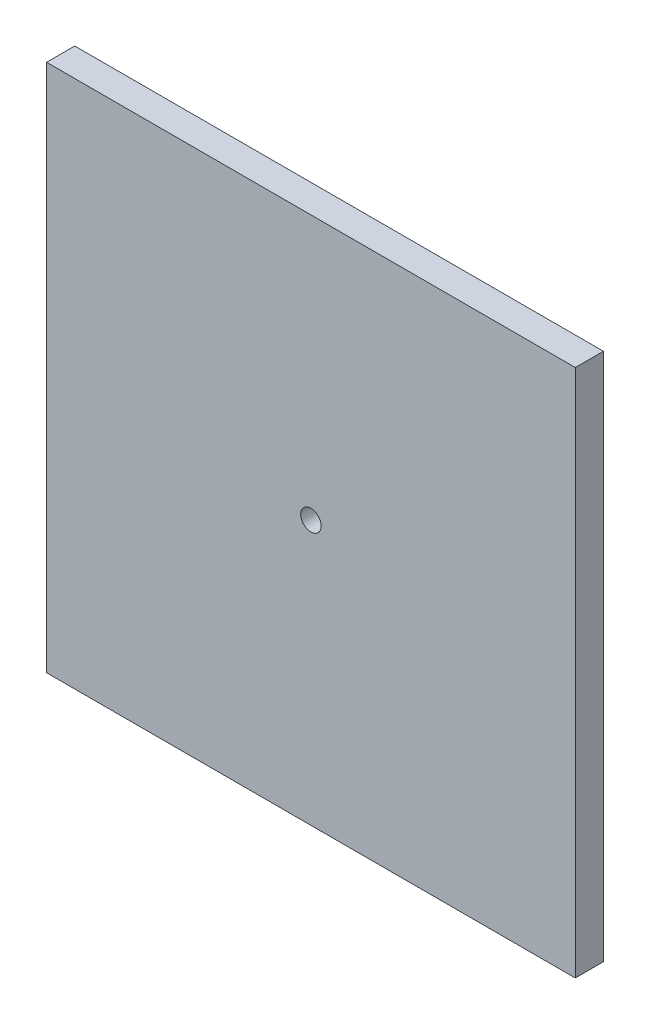
SolidWorks part; units mm, degrees
ref_plane "Front Plane" through (0, 0, 0) normal (0, 0, 1) x (1, 0, 0)
ref_plane "Top Plane" through (0, 0, 0) normal (0, 1, 0) x (1, 0, 0)
ref_plane "Right Plane" through (0, 0, 0) normal (1, 0, 0) x (0, 0, -1)
sketch "Sketch1" plane through (0, 0, 0) normal (0, 0, 1) x (1, 0, 0)
  line L0 (0, 0) -> (-19.5465, -53.7034) construction
  line L1 (-81.9785, 81.9785) -> (81.9785, 81.9785)
  line L2 (-81.9785, 81.9785) -> (-81.9785, -81.9785)
  line L3 (-81.9785, -81.9785) -> (81.9785, -81.9785)
  line L4 (81.9785, 81.9785) -> (81.9785, -81.9785)
  line L5 (0, 0) -> (0, -76.2) construction
  line L6 (-27.4443, 76.2) -> (31.5245, 76.2) construction
  circle A0 centre (0, 0) radius 76.2
  circle A1 centre (-19.5465, -53.7034) radius 3.175
  circle A2 centre (0, 0) radius 3.175
  circle A3 centre (-36.7353, 43.7794) radius 3.175
  circle A4 centre (56.2818, 9.924) radius 3.175
  circle A5 centre (-69.2785, 69.2785) radius 3.175
  circle A6 centre (69.2785, 69.2785) radius 3.175
  circle A7 centre (69.2785, -69.2785) radius 3.175
  circle A8 centre (-69.2785, -69.2785) radius 3.175
  point P12 (0, 81.9785)
  point P18 (0, 0)
  point P23 (-81.9785, 0)
  point P29 (0, 0)
  dimension "D1" = 152.4
  dimension "D4" = 6.35
  dimension "D5" = 6.35
  dimension "D7" = 6.35
  dimension "D2" = 57.15
  dimension "D3" = 20
  dimension "D8" = 12.7
  dimension "D9" = 90
  dimension "D10" = 12.7
  dimension "D11" = 4
  dimension "D12" = 81.9785
  dimension "D13" = 5.7785
  dimension "D6" = 3
extrude "Boss-Extrude1" add sketch "Sketch1" along normal blind 8.7312 contours L4 L1 L2 L3 A8 A7 A6 A5 A0 | A6 | A5 | A8 | A7 | A1 | A3 | A4 | A0 A4 A3 A2 A1 region at (0, 79.6598, 0) region at (-74.0447, 0, 0) region at (-19.5465, -53.7034, 0) region at (-36.7353, 43.7794, 0) region at (56.2818, 9.924, 0) region at (-69.2785, 69.2785, 0) region at (69.2785, 69.2785, 0) region at (69.2785, -69.2785, 0) region at (-69.2785, -69.2785, 0)
extrude "Boss-Extrude4" add sketch "Sketch1<5>" against normal blind 9.398 contours A6 | A5 | A8 | A7 region at (-69.2785, 69.2785, 0) region at (69.2785, 69.2785, 0) region at (69.2785, -69.2785, 0) region at (-69.2785, -69.2785, 0)
sketch "Sketch1<5>" plane through (0, 0, 0) normal (0, 0, 1) x (1, 0, 0) same geometry as "Sketch1"
